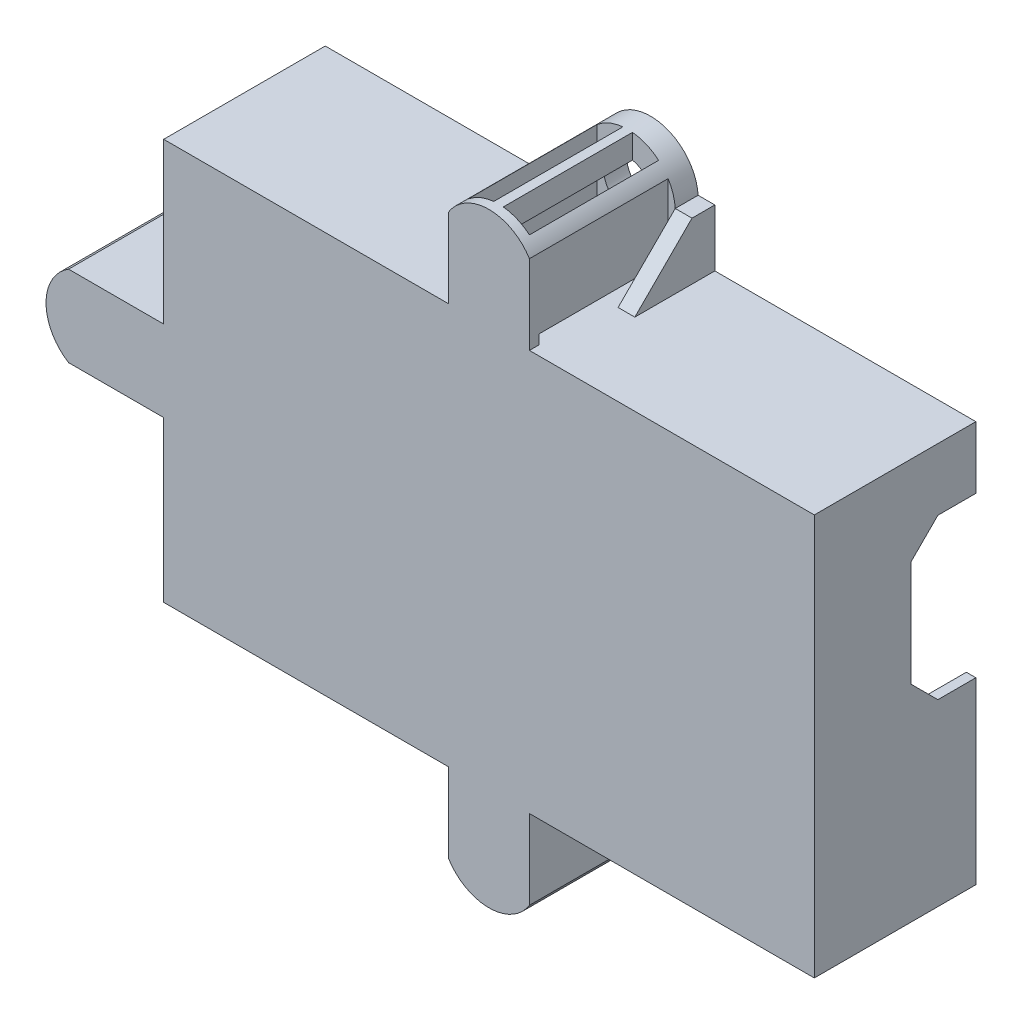
SolidWorks part; units mm, degrees
ref_plane "Front Plane" through (0, 0, 0) normal (0, 0, 1) x (1, 0, 0)
ref_plane "Top Plane" through (0, 0, 0) normal (0, 1, 0) x (1, 0, 0)
ref_plane "Right Plane" through (0, 0, 0) normal (1, 0, 0) x (0, 0, -1)
sketch "Sketch1" plane through (0, 0, 0) normal (0, 0, 1) x (1, 0, 0)
  line L0 (-16.375, 9.825) -> (16.375, -9.825) construction
  line L1 (-16.375, -9.825) -> (-16.575, -9.825) construction
  line L2 (16.575, 10.025) -> (-16.575, 10.025)
  line L3 (16.575, 10.025) -> (16.575, -10.025)
  line L4 (-16.375, 9.825) -> (-16.375, -9.825)
  line L5 (-16.375, -9.825) -> (16.375, -9.825)
  line L6 (16.375, -9.825) -> (16.375, 9.825)
  line L7 (16.375, 9.825) -> (-16.375, 9.825)
  line L8 (-16.375, 9.825) -> (-16.375, -9.825)
  line L9 (-16.375, -9.825) -> (16.375, -9.825)
  line L10 (16.375, -9.825) -> (16.375, 9.825)
  line L11 (16.375, 9.825) -> (-16.375, 9.825)
  line L12 (16.575, -10.025) -> (-16.575, -10.025)
  line L13 (-16.575, 10.025) -> (-16.575, -10.025)
  line L14 (16.575, 10.025) -> (-16.575, -10.025) construction
  line L15 (-13.9701, -11.875) -> (-3.4641, -11.875)
  line L18 (3.4641, -11.875) -> (13.9701, -11.875)
  line L19 (14.8161, -12.3418) -> (24.6724, -27.981)
  line L20 (31.4404, -23.7156) -> (19.404, -4.6171)
  line L21 (19.25, -4.084) -> (19.25, 4.084)
  line L22 (19.404, 4.6171) -> (31.4404, 23.7156)
  line L23 (24.6724, 27.981) -> (14.8161, 12.3418)
  line L24 (13.9701, 11.875) -> (3.4641, 11.875)
  line L25 (-3.4641, 11.875) -> (-13.9701, 11.875)
  line L26 (-14.8161, 12.3418) -> (-24.6724, 27.981)
  line L27 (-31.4404, 23.7156) -> (-19.404, 4.6171)
  line L28 (-19.25, 4.084) -> (-19.25, 3.4641)
  line L29 (-19.25, -3.4641) -> (-19.25, -4.084)
  line L30 (-19.404, -4.6171) -> (-31.4404, -23.7156)
  line L31 (-24.6724, -27.981) -> (-14.8161, -12.3418)
  line L32 (-13.9701, -11.875) -> (-3.4641, -11.875)
  line L33 (3.4641, -11.875) -> (13.9701, -11.875)
  line L34 (14.8161, -12.3418) -> (24.6724, -27.981)
  line L35 (31.4404, -23.7156) -> (19.404, -4.6171)
  line L36 (19.25, -4.084) -> (19.25, 4.084)
  line L37 (19.404, 4.6171) -> (31.4404, 23.7156)
  line L38 (24.6724, 27.981) -> (14.8161, 12.3418)
  line L39 (13.9701, 11.875) -> (3.4641, 11.875)
  line L40 (-3.4641, 11.875) -> (-13.9701, 11.875)
  line L41 (-14.8161, 12.3418) -> (-24.6724, 27.981)
  line L42 (-31.4404, 23.7156) -> (-19.404, 4.6171)
  line L43 (-19.25, 4.084) -> (-19.25, 3.4641)
  line L44 (-19.25, -3.4641) -> (-19.25, -4.084)
  line L45 (-19.404, -4.6171) -> (-31.4404, -23.7156)
  line L46 (-24.6724, -27.981) -> (-14.8161, -12.3418)
  line L47 (16.575, -10.025) -> (-16.575, 10.025) construction
  line L48 (-16.375, -9.825) -> (-16.375, -10.025) construction
  line L49 (-16.575, -10.025) -> (-17.075, -10.025) construction
  line L50 (17.075, 10.525) -> (-17.075, 10.525)
  line L51 (17.075, 10.525) -> (17.075, -10.525)
  line L52 (17.075, -10.525) -> (-17.075, -10.525)
  line L53 (-17.075, 10.525) -> (-17.075, -10.525)
  line L54 (17.075, 10.525) -> (-17.075, -10.525) construction
  line L55 (17.075, -10.525) -> (-17.075, 10.525) construction
  line L56 (-16.575, -10.025) -> (-16.575, -10.525) construction
  line L57 (-20.3929, -2.4744) -> (-17.075, -2.4744)
  line L58 (-20.3929, 2.4744) -> (-17.075, 2.4744)
  line L59 (-2.4744, -13.0179) -> (-2.4744, -10.525)
  line L60 (2.4744, -13.0179) -> (2.4744, -10.525)
  line L61 (-2.4744, 13.0179) -> (-2.4744, 10.525)
  line L62 (2.4744, 13.0179) -> (2.4744, 10.525)
  circle A0 centre (0, -13.375) radius 1.25
  circle A1 centre (-20.75, 0) radius 1.25
  circle A2 centre (0, 13.375) radius 1.25
  arc A32 (-2.4744, -13.0179) -> (-3.4641, -11.875) centre (-3.4641, -12.875) ccw
  arc A33 (-2.4744, -13.0179) -> (2.4744, -13.0179) centre (0, -13.375) ccw
  arc A34 (3.4641, -11.875) -> (2.4744, -13.0179) centre (3.4641, -12.875) ccw
  arc A35 (14.8161, -12.3418) -> (13.9701, -11.875) centre (13.9701, -12.875) ccw
  arc A36 (24.7505, -28.8963) -> (24.6724, -27.981) centre (23.8264, -28.5142) ccw
  arc A37 (24.7505, -28.8963) -> (32.2325, -24.1809) centre (31.8198, -31.8198) ccw
  arc A38 (31.4404, -23.7156) -> (32.2325, -24.1809) centre (32.2864, -23.1824) ccw
  arc A39 (19.25, -4.084) -> (19.404, -4.6171) centre (20.25, -4.084) ccw
  arc A40 (19.404, 4.6171) -> (19.25, 4.084) centre (20.25, 4.084) ccw
  arc A41 (32.2325, 24.1809) -> (31.4404, 23.7156) centre (32.2864, 23.1824) ccw
  arc A42 (32.2325, 24.1809) -> (24.7505, 28.8963) centre (31.8198, 31.8198) ccw
  arc A43 (24.6724, 27.981) -> (24.7505, 28.8963) centre (23.8264, 28.5142) ccw
  arc A44 (13.9701, 11.875) -> (14.8161, 12.3418) centre (13.9701, 12.875) ccw
  arc A45 (2.4744, 13.0179) -> (3.4641, 11.875) centre (3.4641, 12.875) ccw
  arc A46 (2.4744, 13.0179) -> (-2.4744, 13.0179) centre (0, 13.375) ccw
  arc A47 (-3.4641, 11.875) -> (-2.4744, 13.0179) centre (-3.4641, 12.875) ccw
  arc A48 (-14.8161, 12.3418) -> (-13.9701, 11.875) centre (-13.9701, 12.875) ccw
  arc A49 (-24.7505, 28.8963) -> (-24.6724, 27.981) centre (-23.8264, 28.5142) ccw
  arc A50 (-24.7505, 28.8963) -> (-32.2325, 24.1809) centre (-31.8198, 31.8198) ccw
  arc A51 (-31.4404, 23.7156) -> (-32.2325, 24.1809) centre (-32.2864, 23.1824) ccw
  arc A52 (-19.25, 4.084) -> (-19.404, 4.6171) centre (-20.25, 4.084) ccw
  arc A53 (-20.3929, 2.4744) -> (-19.25, 3.4641) centre (-20.25, 3.4641) ccw
  arc A54 (-20.3929, 2.4744) -> (-20.3929, -2.4744) centre (-20.75, 0) ccw
  arc A55 (-19.25, -3.4641) -> (-20.3929, -2.4744) centre (-20.25, -3.4641) ccw
  arc A56 (-19.404, -4.6171) -> (-19.25, -4.084) centre (-20.25, -4.084) ccw
  arc A57 (-32.2325, -24.1809) -> (-31.4404, -23.7156) centre (-32.2864, -23.1824) ccw
  arc A58 (-32.2325, -24.1809) -> (-24.7505, -28.8963) centre (-31.8198, -31.8198) ccw
  arc A59 (-24.6724, -27.981) -> (-24.7505, -28.8963) centre (-23.8264, -28.5142) ccw
  arc A60 (-13.9701, -11.875) -> (-14.8161, -12.3418) centre (-13.9701, -12.875) ccw
  arc A61 (-2.4744, -13.0179) -> (-3.4641, -11.875) centre (-3.4641, -12.875) ccw
  arc A62 (-2.4744, -13.0179) -> (2.4744, -13.0179) centre (0, -13.375) ccw
  arc A63 (3.4641, -11.875) -> (2.4744, -13.0179) centre (3.4641, -12.875) ccw
  arc A64 (14.8161, -12.3418) -> (13.9701, -11.875) centre (13.9701, -12.875) ccw
  arc A65 (24.7505, -28.8963) -> (24.6724, -27.981) centre (23.8264, -28.5142) ccw
  arc A66 (24.7505, -28.8963) -> (32.2325, -24.1809) centre (31.8198, -31.8198) ccw
  arc A67 (31.4404, -23.7156) -> (32.2325, -24.1809) centre (32.2864, -23.1824) ccw
  arc A68 (19.25, -4.084) -> (19.404, -4.6171) centre (20.25, -4.084) ccw
  arc A69 (19.404, 4.6171) -> (19.25, 4.084) centre (20.25, 4.084) ccw
  arc A70 (32.2325, 24.1809) -> (31.4404, 23.7156) centre (32.2864, 23.1824) ccw
  arc A71 (32.2325, 24.1809) -> (24.7505, 28.8963) centre (31.8198, 31.8198) ccw
  arc A72 (24.6724, 27.981) -> (24.7505, 28.8963) centre (23.8264, 28.5142) ccw
  arc A73 (13.9701, 11.875) -> (14.8161, 12.3418) centre (13.9701, 12.875) ccw
  arc A74 (2.4744, 13.0179) -> (3.4641, 11.875) centre (3.4641, 12.875) ccw
  arc A75 (2.4744, 13.0179) -> (-2.4744, 13.0179) centre (0, 13.375) ccw
  arc A76 (-3.4641, 11.875) -> (-2.4744, 13.0179) centre (-3.4641, 12.875) ccw
  arc A77 (-14.8161, 12.3418) -> (-13.9701, 11.875) centre (-13.9701, 12.875) ccw
  arc A78 (-24.7505, 28.8963) -> (-24.6724, 27.981) centre (-23.8264, 28.5142) ccw
  arc A79 (-24.7505, 28.8963) -> (-32.2325, 24.1809) centre (-31.8198, 31.8198) ccw
  arc A80 (-31.4404, 23.7156) -> (-32.2325, 24.1809) centre (-32.2864, 23.1824) ccw
  arc A81 (-19.25, 4.084) -> (-19.404, 4.6171) centre (-20.25, 4.084) ccw
  arc A82 (-20.3929, 2.4744) -> (-19.25, 3.4641) centre (-20.25, 3.4641) ccw
  arc A83 (-20.3929, 2.4744) -> (-20.3929, -2.4744) centre (-20.75, 0) ccw
  arc A84 (-19.25, -3.4641) -> (-20.3929, -2.4744) centre (-20.25, -3.4641) ccw
  arc A85 (-19.404, -4.6171) -> (-19.25, -4.084) centre (-20.25, -4.084) ccw
  arc A86 (-32.2325, -24.1809) -> (-31.4404, -23.7156) centre (-32.2864, -23.1824) ccw
  arc A87 (-32.2325, -24.1809) -> (-24.7505, -28.8963) centre (-31.8198, -31.8198) ccw
  arc A88 (-24.6724, -27.981) -> (-24.7505, -28.8963) centre (-23.8264, -28.5142) ccw
  arc A89 (-13.9701, -11.875) -> (-14.8161, -12.3418) centre (-13.9701, -12.875) ccw
  point P6 (0, 0)
  point P25 (0, 0)
  dimension "D4" = 0.5
  dimension "D5" = 2.5
  dimension "D1" = 0
  dimension "D2" = 0
  dimension "D3" = 0.2
extrude "Boss-Extrude1" add sketch "Sketch1" along normal offset from surface (7.98 mm away) 2.5 contours A84 L57 L53 L58 A82 A83 | L50 L53 L52 L51 L13 L2 L3 L12 | A63 L60 L52 L59 A61 A62 | A76 L61 L50 L62 A74 A75 region at (-2.4011, -11.6286, 0) region at (-9.7747, -10.1238, 0) region at (-18.5911, -2.3949, 0) region at (0, 10.5982, 0) offset beyond the face yes
sketch "Sketch2" plane through (0, 0, 7.98) normal (0, 0, 1) x (1, 0, 0)
  line L0 (-2.5, 10.525) -> (2.4744, 10.525)
  line L1 (-17.075, 2.5) -> (-17.075, -2.5)
  line L2 (-2.5, -10.525) -> (2.4744, -10.525)
  line L6 (-20.1071, -2.4744) -> (-17.075, -2.4744)
  line L7 (-20.1071, -2.4744) -> (-17.075, -2.4744)
  line L8 (-17.075, -2.4744) -> (-17.075, -10.525)
  line L9 (-17.075, -2.4744) -> (-17.075, -10.525)
  line L20 (-17.075, -10.525) -> (-2.4744, -10.525)
  line L21 (-17.075, -10.525) -> (-2.4744, -10.525)
  line L22 (-2.4744, -10.525) -> (-2.4744, -12.7321)
  line L23 (-2.4744, -10.525) -> (-2.4744, -12.7321)
  line L24 (2.4744, -12.7321) -> (2.4744, -10.525)
  line L25 (2.4744, -12.7321) -> (2.4744, -10.525)
  line L26 (2.4744, -10.525) -> (17.075, -10.525)
  line L27 (2.4744, -10.525) -> (17.075, -10.525)
  line L28 (17.075, -10.525) -> (17.075, 10.525)
  line L29 (17.075, -10.525) -> (17.075, 10.525)
  line L30 (17.075, 10.525) -> (2.4744, 10.525)
  line L31 (17.075, 10.525) -> (2.4744, 10.525)
  line L32 (2.4744, 10.525) -> (2.4744, 12.7321)
  line L33 (2.4744, 10.525) -> (2.4744, 12.7321)
  line L34 (-2.4744, 12.7321) -> (-2.4744, 10.525)
  line L35 (-2.4744, 12.7321) -> (-2.4744, 10.525)
  line L36 (-2.4744, 10.525) -> (-17.075, 10.525)
  line L37 (-2.4744, 10.525) -> (-17.075, 10.525)
  line L38 (-17.075, 10.525) -> (-17.075, 2.4744)
  line L39 (-17.075, 10.525) -> (-17.075, 2.4744)
  line L40 (-17.075, 2.4744) -> (-20.1071, 2.4744)
  line L41 (-17.075, 2.4744) -> (-20.1071, 2.4744)
  arc A9 (-20.1071, -2.4744) -> (-20.3929, -2.4744) centre (-20.25, -3.4641) ccw
  arc A10 (-20.1071, -2.4744) -> (-20.3929, -2.4744) centre (-20.25, -3.4641) ccw
  arc A11 (-2.4744, -13.0179) -> (-2.4744, -12.7321) centre (-3.4641, -12.875) ccw
  arc A12 (-2.4744, -13.0179) -> (-2.4744, -12.7321) centre (-3.4641, -12.875) ccw
  arc A13 (-2.4744, -13.0179) -> (2.4744, -13.0179) centre (0, -13.375) ccw
  arc A14 (-2.4744, -13.0179) -> (2.4744, -13.0179) centre (0, -13.375) ccw
  arc A15 (2.4744, -12.7321) -> (2.4744, -13.0179) centre (3.4641, -12.875) ccw
  arc A16 (2.4744, -12.7321) -> (2.4744, -13.0179) centre (3.4641, -12.875) ccw
  arc A17 (2.4744, 13.0179) -> (2.4744, 12.7321) centre (3.4641, 12.875) ccw
  arc A18 (2.4744, 13.0179) -> (2.4744, 12.7321) centre (3.4641, 12.875) ccw
  arc A19 (2.4744, 13.0179) -> (-2.4744, 13.0179) centre (0, 13.375) ccw
  arc A20 (2.4744, 13.0179) -> (-2.4744, 13.0179) centre (0, 13.375) ccw
  arc A21 (-2.4744, 12.7321) -> (-2.4744, 13.0179) centre (-3.4641, 12.875) ccw
  arc A22 (-2.4744, 12.7321) -> (-2.4744, 13.0179) centre (-3.4641, 12.875) ccw
  arc A23 (-20.3929, 2.4744) -> (-20.1071, 2.4744) centre (-20.25, 3.4641) ccw
  arc A24 (-20.3929, 2.4744) -> (-20.1071, 2.4744) centre (-20.25, 3.4641) ccw
  arc A25 (-20.3929, 2.4744) -> (-20.3929, -2.4744) centre (-20.75, 0) ccw
  arc A26 (-20.3929, 2.4744) -> (-20.3929, -2.4744) centre (-20.75, 0) ccw
  dimension "D1" = 0
extrude "Cut-Extrude1" cut sketch "Sketch2" against normal offset from surface (6.78 mm away) 1.2 contours L0 | L1 | L2 region at (0, 12.9704, 7.98) region at (-19.9289, 0, 7.98) region at (0, -12.9704, 7.98) up to face at (-5.364, 0, 0)
sketch "Sketch3" plane through (17.075, 0, 0) normal (1, 0, 0) x (0, 0, -1)
  line L0 (0, 10.525) -> (0, -10.525) construction
  line L1 (0, 7.265) -> (-3.395, 7.265)
  line L2 (0, 7.265) -> (0, -1.115)
  line L3 (0, -1.115) -> (-3.395, -1.115)
  line L4 (-3.395, 7.265) -> (-3.395, -1.115)
  line L6 (-1.3, 7.065) -> (-1.3, 7.265) construction
  line L7 (-1.3, -0.915) -> (-1.3, -1.115) construction
  line L8 (-3.195, 5.375) -> (-3.395, 5.375) construction
  dimension "D1" = 0.2
extrude "Cut-Extrude2" cut sketch "Sketch3" against normal up to next
chamfer "Chamfer1" distance 1.4 angle 45 2 edges at (16.825, -1.115, 3.395) (16.825, 7.265, 3.395)
sketch "Sketch4" plane through (0, 0, 7.98) normal (0, 0, 1) x (1, 0, 0)
  line L4 (-17.075, 10.525) -> (-17.075, -10.525)
  line L8 (-17.075, 10.525) -> (-17.075, -10.525)
  line L17 (-17.075, -10.525) -> (17.075, -10.525)
  line L18 (-17.075, -10.525) -> (17.075, -10.525)
  line L25 (17.075, -10.525) -> (17.075, 10.525)
  line L26 (17.075, -10.525) -> (17.075, 10.525)
  line L27 (17.075, 10.525) -> (-17.075, 10.525)
  line L28 (17.075, 10.525) -> (-17.075, 10.525)
  dimension "D1" = 0
extrude "Boss-Extrude2" add sketch "Sketch4" along normal blind 0.5
sketch "Sketch8" plane through (-17.075, 0, 0) normal (-1, 0, 0) x (0, 0, 1)
  line L1 (5.93, 3.385) -> (7.98, 3.385)
  line L2 (5.93, 3.385) -> (5.93, -3.385)
  line L3 (5.93, -3.385) -> (7.98, -3.385)
  line L4 (7.98, 3.385) -> (7.98, -3.385)
  line L7 (7.08, 3.385) -> (5.93, 3.385) construction
  line L8 (5.93, -3.385) -> (7.08, -3.385) construction
  line L9 (5.93, 3.385) -> (5.93, 2.4) construction
  line L10 (7.98, -3.985) -> (7.98, -2.4) construction
extrude "Cut-Extrude3" cut sketch "Sketch8" against normal up to next
sketch "Sketch9" plane through (0, 0, 7.98) normal (0, 0, -1) x (-1, 0, 0)
  line L1 (16.575, 2.4) -> (17.075, 2.4)
  line L2 (16.575, 2.4) -> (16.575, 3.385)
  line L3 (16.575, 3.385) -> (17.075, 3.385)
  line L4 (17.075, 2.4) -> (17.075, 3.385)
  line L5 (16.575, -2.4) -> (17.075, -2.4)
  line L6 (16.575, -2.4) -> (16.575, -3.385)
  line L7 (16.575, -3.385) -> (17.075, -3.385)
  line L8 (17.075, -2.4) -> (17.075, -3.385)
extrude "Boss-Extrude6" add sketch "Sketch9" along normal blind 0.8
sketch "Sketch11" plane through (0, 0, 7.98) normal (0, 0, -1) x (-1, 0, 0)
  line L24 (16.675, -4.085) -> (16.675, -2.3)
  line L25 (16.675, -2.3) -> (15.385, -2.3)
  line L26 (15.385, -2.3) -> (15.385, 2.3)
  line L27 (15.385, 2.3) -> (16.675, 2.3)
  line L28 (16.675, 2.3) -> (16.675, 4.085)
  line L29 (16.675, 4.085) -> (10.255, 4.085)
  line L30 (10.255, 4.085) -> (10.255, 2.4)
  line L31 (10.255, 2.4) -> (5.655, 2.4)
  line L32 (5.655, 2.4) -> (5.655, -2.4)
  line L33 (5.655, -2.4) -> (10.255, -2.4)
  line L34 (10.255, -2.4) -> (10.255, -4.085)
  line L35 (10.255, -4.085) -> (16.675, -4.085)
  line L36 (16.675, -4.085) -> (16.675, -2.3)
  line L37 (16.675, -2.3) -> (15.385, -2.3)
  line L38 (15.385, -2.3) -> (15.385, 2.3)
  line L39 (15.385, 2.3) -> (16.675, 2.3)
  line L40 (16.675, 2.3) -> (16.675, 4.085)
  line L41 (16.675, 4.085) -> (10.255, 4.085)
  line L42 (10.255, 4.085) -> (10.255, 2.4)
  line L43 (10.255, 2.4) -> (5.655, 2.4)
  line L44 (5.655, 2.4) -> (5.655, -2.4)
  line L45 (5.655, -2.4) -> (10.255, -2.4)
  line L46 (10.255, -2.4) -> (10.255, -4.085)
  line L47 (10.255, -4.085) -> (16.675, -4.085)
  line L48 (5.655, 1.9) -> (3.655, 1.9)
  line L49 (3.655, 0) -> (17.385, 0) construction
  line L50 (5.655, -1.9) -> (3.655, -1.9)
  line L51 (16.575, 6.085) -> (16.575, 4.085)
  line L53 (16.575, 10.025) -> (16.575, 2.4) construction
  line L54 (16.575, -6.085) -> (16.575, -4.085)
  line L55 (16.575, -2.4) -> (16.575, -10.025) construction
  line L60 (18.675, -6.085) -> (18.675, -0.3)
  line L61 (18.675, -0.3) -> (17.385, -0.3)
  line L62 (17.385, -0.3) -> (17.385, 0.3)
  line L63 (17.385, 0.3) -> (18.675, 0.3)
  line L64 (18.675, 0.3) -> (18.675, 6.085)
  line L65 (18.675, 6.085) -> (8.255, 6.085)
  line L66 (8.255, 6.085) -> (8.255, 4.4)
  line L67 (8.255, 4.4) -> (3.655, 4.4)
  line L68 (3.655, 4.4) -> (3.655, -4.4)
  line L69 (3.655, -4.4) -> (8.255, -4.4)
  line L70 (8.255, -4.4) -> (8.255, -6.085)
  line L71 (8.255, -6.085) -> (18.675, -6.085)
  line L72 (18.675, -6.085) -> (18.675, -0.3)
  line L73 (18.675, -0.3) -> (17.385, -0.3)
  line L74 (17.385, -0.3) -> (17.385, 0.3)
  line L75 (17.385, 0.3) -> (18.675, 0.3)
  line L76 (18.675, 0.3) -> (18.675, 6.085)
  line L77 (18.675, 6.085) -> (8.255, 6.085)
  line L78 (8.255, 6.085) -> (8.255, 4.4)
  line L79 (8.255, 4.4) -> (3.655, 4.4)
  line L80 (3.655, 4.4) -> (3.655, -4.4)
  line L81 (3.655, -4.4) -> (8.255, -4.4)
  line L82 (8.255, -4.4) -> (8.255, -6.085)
  line L83 (8.255, -6.085) -> (18.675, -6.085)
  line M27 (16.575, -10.025) -> (16.575, -2.4)
  line M31 (16.575, 2.4) -> (16.575, 10.025)
  dimension "D3" = 0.5
  dimension "D1" = 0.1
  dimension "D2" = 2.1
extrude "Boss-Extrude7" add sketch "Sketch11" along normal blind 2.5 contours L79 L80 L48 L44 L43 L42 L41 L77 L78 M31 | L82 L83 L47 L46 L45 L44 L50 L80 L81 M27 region at (-9.8383, -4.2692, 7.98) region at (-9.8383, 4.2692, 7.98)
sketch "Sketch12" plane through (0, 0, 7.98) normal (0, 0, -1) x (-1, 0, 0)
  line L0 (16.575, -6.085) -> (16.575, -10.025) construction
  line L1 (-3.0335, 0) -> (1.6631, 0) construction
  line L2 (16.575, 8.055) -> (14.605, 8.055)
  line L3 (16.575, 8.055) -> (16.575, 6.085)
  line L4 (16.575, 6.085) -> (14.605, 6.085)
  line L5 (16.575, -8.055) -> (14.605, -8.055)
  line L6 (16.575, -8.055) -> (16.575, -6.085)
  line L7 (16.575, -6.085) -> (14.605, -6.085)
  line L8 (14.605, -8.055) -> (14.605, -6.085)
  line L9 (8.255, -6.085) -> (16.575, -6.085) construction
  line L10 (14.605, 8.055) -> (14.605, 6.085)
  line L11 (-16.575, 10.025) -> (-16.575, -10.025) construction
  line L12 (-14.605, 2) -> (-16.575, 2)
  line L13 (-14.605, 2) -> (-14.605, -2)
  line L14 (-14.605, -2) -> (-16.575, -2)
  line L15 (-16.575, 2) -> (-16.575, -2)
  line L16 (-14.605, 2) -> (-16.575, -2) construction
  line L17 (-14.605, -2) -> (-16.575, 2) construction
  point P16 (-15.59, 0)
  dimension "D1" = 4
extrude "Boss-Extrude8" add sketch "Sketch12" along normal up to surface (3.95 mm away)
sketch "Sketch13" plane through (-17.075, 0, 0) normal (-1, 0, 0) x (0, 0, 1)
  line L0 (7.18, 2.4) -> (7.18, 3.385) construction
  line L1 (7.98, 2.4) -> (7.18, 2.4)
  line L2 (7.98, 2.4) -> (7.98, 2.9)
  line L3 (7.98, 2.9) -> (7.18, 2.9)
  line L4 (7.18, 2.4) -> (7.18, 2.9)
  line L5 (5.93, 0) -> (7.98, 0) construction
  line L6 (7.18, 3.385) -> (5.43, 3.385)
  line L7 (7.18, 3.385) -> (7.18, 3.885)
  line L8 (7.18, 3.885) -> (5.43, 3.885)
  line L9 (5.43, 3.385) -> (5.43, 3.885)
  line L10 (5.93, 3.385) -> (5.93, -3.385) construction
  line L11 (7.98, -2) -> (7.98, 2) construction
  line L12 (5.43, 1.6925) -> (5.93, 1.6925) construction
  line L13 (5.43, 3.385) -> (5.93, 3.385)
  line L14 (5.43, 3.385) -> (5.43, -3.385)
  line L15 (5.93, 0) -> (5.93, -3.385)
  line L16 (5.93, 3.385) -> (5.93, 0)
  line L17 (7.98, -2.4) -> (7.98, -2.9)
  line L18 (7.98, -2.9) -> (7.18, -2.9)
  line L19 (7.18, -3.385) -> (7.18, -3.885)
  line L20 (7.18, -3.885) -> (5.43, -3.885)
  line L21 (5.43, -3.385) -> (5.43, -3.885)
  line L22 (5.43, 3.385) -> (5.43, -3.385)
  line L23 (1.2, -2.5) -> (1.2, 2.5) construction
  line L24 (0, 3.3744) -> (1.2, 3.3744)
  line L25 (0, 3.3744) -> (0, 5.8744)
  line L26 (0, 5.8744) -> (1.2, 5.8744)
  line L27 (1.2, 3.3744) -> (1.2, 5.8744)
  line L28 (1.2, 2.4744) -> (0, 2.4744) construction
  line L29 (0, 10.525) -> (0, 2.4744) construction
  line M12 (7.98, -2.4) -> (7.18, -2.4)
  line M13 (7.18, -2.4) -> (7.18, -3.385)
  line M14 (7.18, -3.385) -> (5.93, -3.385)
  line M15 (5.93, -3.385) -> (5.93, 3.385)
  line M16 (5.93, 3.385) -> (7.18, 3.385)
  line M17 (7.18, 3.385) -> (7.18, 2.4)
  line M18 (7.18, 2.4) -> (7.98, 2.4)
  line M22 (0, 10.525) -> (0, 2.4744)
  dimension "D1" = 0.5
  dimension "D2" = 2.5
  dimension "D3" = 0.9
extrude "Cut-Extrude4" cut sketch "Sketch13" against normal up to next contours L9 L6 L7 L8 M16 | L2 L3 M17 M18 | L14 L21 L20 L19 L6 M14 M15 | L18 L17 M12 M13 | L24 L27 L26 M22 region at (-17.075, -2.65, 7.58) region at (-17.075, 3.635, 6.305) region at (-17.075, 2.65, 7.58) region at (-17.075, -0.7466, 5.8084) region at (-17.075, 4.6244, 0.6)
sketch "Sketch14" plane through (0, 0, 5.48) normal (0, 0, -1) x (-1, 0, 0)
  line L0 (16.575, 4.085) -> (10.255, 4.085) construction
  line L1 (16.575, 6.085) -> (14.175, 6.085)
  line L2 (16.575, 6.085) -> (16.575, 3.685)
  line L3 (16.575, 3.685) -> (14.175, 3.685)
  line L4 (14.175, 6.085) -> (14.175, 3.685)
  line L5 (3.655, 1.9) -> (3.655, -1.9) construction
  line L6 (3.655, 0) -> (16.575, 0) construction
  line L8 (16.575, -6.085) -> (16.575, -3.685)
  line L9 (16.575, -6.085) -> (14.175, -6.085)
  line L10 (14.175, -6.085) -> (14.175, -3.685)
  line L11 (16.575, -3.685) -> (14.175, -3.685)
  line L12 (5.655, 2.4) -> (5.655, 1.9) construction
  line L13 (3.655, 4.4) -> (5.655, 4.4)
  line L14 (3.655, 4.4) -> (3.655, 1.5)
  line L15 (3.655, 1.5) -> (5.655, 1.5)
  line L16 (5.655, 4.4) -> (5.655, 1.5)
  line L17 (15.375, 3.685) -> (15.375, 4.085) construction
  line L18 (16.575, 4.085) -> (10.255, 4.085) construction
  line L19 (4.655, 1.5) -> (4.655, 1.9) construction
  line L20 (5.655, 1.9) -> (3.655, 1.9) construction
  line L21 (3.655, -4.4) -> (5.655, -4.4)
  line L22 (5.655, -4.4) -> (5.655, -1.5)
  line L23 (3.655, -1.5) -> (5.655, -1.5)
  line L24 (3.655, -4.4) -> (3.655, -1.5)
  line L25 (16.575, 3.3744) -> (16.575, -10.025) construction
  dimension "D1" = 0.4
extrude "Boss-Extrude9" add sketch "Sketch14" along normal blind 0.6
ref_plane "Plane1" through (0, 0, 2.95) normal (0, 0, -1) x (-1, 0, 0)
sketch "Sketch16" plane through (0, 0, 2.95) normal (0, 0, -1) x (-1, 0, 0)
  line L0 (-16.575, 10.025) -> (16.575, 10.025) construction
  line L1 (6.075, 10.025) -> (8.575, 10.025)
  line L2 (6.075, 10.025) -> (6.075, 9.325)
  line L3 (6.075, 9.325) -> (8.575, 9.325)
  line L4 (8.575, 10.025) -> (8.575, 9.325)
  line L6 (16.575, 10.025) -> (16.575, 5.8744) construction
  line L8 (-16.575, 10.025) -> (-14.075, 10.025)
  line L9 (-16.575, 10.025) -> (-16.575, 9.325)
  line L10 (-16.575, 9.325) -> (-14.075, 9.325)
  line L11 (-14.075, 10.025) -> (-14.075, 9.325)
  line L12 (16.575, -10.025) -> (14.075, -10.025)
  line L13 (16.575, -10.025) -> (16.575, -9.325)
  line L14 (16.575, -9.325) -> (14.075, -9.325)
  line L15 (14.075, -10.025) -> (14.075, -9.325)
  line L16 (-16.575, -10.025) -> (-14.075, -10.025)
  line L17 (-16.575, -10.025) -> (-16.575, -9.325)
  line L18 (-16.575, -9.325) -> (-14.075, -9.325)
  line L19 (-14.075, -10.025) -> (-14.075, -9.325)
  dimension "D1" = 2.5
  dimension "D2" = 0.7
  dimension "D3" = 8
extrude "Boss-Extrude13" add sketch "Sketch16" along normal blind 0.8
chamfer "Chamfer2" distance 1 angle 45 2 edges at (-10.255, 3.2425, 5.48) (-10.255, -3.2425, 5.48)
sketch "Sketch17" plane through (0, 0, 1.2) normal (0, 0, 1) x (1, 0, 0)
  line L0 (-23.25, 0) -> (-17.075, 0) construction
  line L1 (-17.075, 10.525) -> (-17.075, -10.525) construction
  line L2 (0, 15.875) -> (0, -15.875) construction
  line L3 (-20.1071, 2.4744) -> (-17.075, 2.4744) construction
  line L4 (-20.075, -3.3744) -> (-17.075, -3.3744)
  line L5 (-20.075, -3.3744) -> (-20.075, 3.3744)
  line L6 (-20.075, 3.3744) -> (-17.075, 3.3744)
  line L7 (-17.075, -3.3744) -> (-17.075, 3.3744)
  line L8 (-20.075, -3.3744) -> (-17.075, 3.3744) construction
  line L9 (-20.075, 3.3744) -> (-17.075, -3.3744) construction
  line L10 (17.075, 10.525) -> (-17.075, 10.525) construction
  line L11 (-3.3744, 10.525) -> (3.3744, 10.525)
  line L12 (-3.3744, 10.525) -> (-3.3744, 13.525)
  line L13 (-20.1071, -2.4744) -> (-17.075, -2.4744)
  line L14 (-17.075, -2.4744) -> (-17.075, 2.4744)
  line L15 (-17.075, 2.4744) -> (-20.1071, 2.4744)
  line L16 (-20.1071, -2.4744) -> (-17.075, -2.4744)
  line L17 (-17.075, -2.4744) -> (-17.075, 2.4744)
  line L18 (-17.075, 2.4744) -> (-20.1071, 2.4744)
  line L19 (-2.4744, 12.7321) -> (-2.4744, 10.525)
  line L20 (-2.4744, 10.525) -> (2.4744, 10.525)
  line L21 (2.4744, 10.525) -> (2.4744, 12.7321)
  line L22 (-2.4744, 12.7321) -> (-2.4744, 10.525)
  line L23 (-2.4744, 10.525) -> (2.4744, 10.525)
  line L24 (2.4744, 10.525) -> (2.4744, 12.7321)
  line L25 (2.4744, -12.7321) -> (2.4744, -10.525)
  line L26 (2.4744, -10.525) -> (-2.4744, -10.525)
  line L27 (-2.4744, -10.525) -> (-2.4744, -12.7321)
  line L28 (2.4744, -12.7321) -> (2.4744, -10.525)
  line L29 (2.4744, -10.525) -> (-2.4744, -10.525)
  line L30 (-2.4744, -10.525) -> (-2.4744, -12.7321)
  line L31 (-3.3744, 13.525) -> (3.3744, 13.525)
  line L32 (3.3744, 10.525) -> (3.3744, 13.525)
  line L33 (-3.3744, 10.525) -> (3.3744, 13.525) construction
  line L34 (-3.3744, 13.525) -> (3.3744, 10.525) construction
  line L35 (-17.075, -10.525) -> (17.075, -10.525) construction
  line L36 (3.3744, -13.525) -> (-3.3744, -13.525)
  line L37 (3.3744, -13.525) -> (3.3744, -10.525)
  line L38 (3.3744, -10.525) -> (-3.3744, -10.525)
  line L39 (-3.3744, -13.525) -> (-3.3744, -10.525)
  line L40 (3.3744, -13.525) -> (-3.3744, -10.525) construction
  line L41 (3.3744, -10.525) -> (-3.3744, -13.525) construction
  arc A0 (-20.3929, 2.4744) -> (-20.3929, -2.4744) centre (-20.75, 0) ccw construction
  arc A1 (2.4744, 13.0179) -> (-2.4744, 13.0179) centre (0, 13.375) ccw construction
  arc A2 (-2.4744, -13.0179) -> (2.4744, -13.0179) centre (0, -13.375) ccw construction
  arc A6 (-20.3929, 2.4744) -> (-20.1071, 2.4744) centre (-20.25, 3.4641) ccw
  arc A7 (-20.3929, 2.4744) -> (-20.3929, -2.4744) centre (-20.75, 0) ccw
  arc A8 (-20.1071, -2.4744) -> (-20.3929, -2.4744) centre (-20.25, -3.4641) ccw
  arc A9 (-20.3929, 2.4744) -> (-20.1071, 2.4744) centre (-20.25, 3.4641) ccw
  arc A10 (-20.3929, 2.4744) -> (-20.3929, -2.4744) centre (-20.75, 0) ccw
  arc A11 (-20.1071, -2.4744) -> (-20.3929, -2.4744) centre (-20.25, -3.4641) ccw
  arc A12 (2.4744, 13.0179) -> (2.4744, 12.7321) centre (3.4641, 12.875) ccw
  arc A13 (2.4744, 13.0179) -> (-2.4744, 13.0179) centre (0, 13.375) ccw
  arc A14 (-2.4744, 12.7321) -> (-2.4744, 13.0179) centre (-3.4641, 12.875) ccw
  arc A15 (2.4744, 13.0179) -> (2.4744, 12.7321) centre (3.4641, 12.875) ccw
  arc A16 (2.4744, 13.0179) -> (-2.4744, 13.0179) centre (0, 13.375) ccw
  arc A17 (-2.4744, 12.7321) -> (-2.4744, 13.0179) centre (-3.4641, 12.875) ccw
  arc A18 (-2.4744, -13.0179) -> (-2.4744, -12.7321) centre (-3.4641, -12.875) ccw
  arc A19 (-2.4744, -13.0179) -> (2.4744, -13.0179) centre (0, -13.375) ccw
  arc A20 (2.4744, -12.7321) -> (2.4744, -13.0179) centre (3.4641, -12.875) ccw
  arc A21 (-2.4744, -13.0179) -> (-2.4744, -12.7321) centre (-3.4641, -12.875) ccw
  arc A22 (-2.4744, -13.0179) -> (2.4744, -13.0179) centre (0, -13.375) ccw
  arc A23 (2.4744, -12.7321) -> (2.4744, -13.0179) centre (3.4641, -12.875) ccw
  point P15 (-18.575, 0)
  point P38 (0, 12.025)
  point P57 (0, -12.025)
  line M26 (2.4744, -12.7321) -> (2.4744, -10.525)
  line M28 (-2.4744, -10.525) -> (-2.4744, -12.7321)
  arc M29 (-2.4744, -12.7321) -> (-2.4744, -13.0179) centre (-3.4641, -12.875) cw
  arc M30 (-2.4744, -13.0179) -> (2.4744, -13.0179) centre (0, -13.375) ccw
  arc M31 (2.4744, -13.0179) -> (2.4744, -12.7321) centre (3.4641, -12.875) cw
  dimension "D1" = 0.9
  dimension "D2" = 3
  dimension "D3" = 0
  dimension "D4" = 0
  dimension "D5" = 0
extrude "Boss-Extrude17" add sketch "Sketch17" against normal up to surface (1.2 mm away) contours L18 L7 L6 L5 | L16 L5 L4 L7 | L22 A17 A16 L31 L12 L11 | A16 A15 L24 L11 L32 L31 | L37 L38 L36 M26 M31 M30 | L39 L36 L38 M30 M29 M28 region at (-18.575, -2.9244, 1.2) region at (-18.575, 2.9244, 1.2) region at (-2.9256, 12.0209, 1.2) region at (2.9256, 12.0209, 1.2) region at (2.9256, -12.0209, 1.2) region at (-2.9256, -12.0209, 1.2) up to face at (-5.9004, -5.5994, 0)
sketch "Sketch18" plane through (0, 0, 1.2) normal (0, 0, 1) x (1, 0, 0)
  line L0 (-17.075, -3.3744) -> (-17.075, 3.3744) construction
  line L1 (-20.075, 3.3744) -> (-17.075, 3.3744)
  line L2 (-20.075, 3.3744) -> (-20.075, 2.4744)
  line L3 (-20.075, 2.4744) -> (-17.075, 2.4744)
  line L4 (-17.075, 3.3744) -> (-17.075, 2.4744)
  line L5 (-17.075, 10.525) -> (-17.075, -10.525) construction
  line L6 (-20.075, -2.4744) -> (-17.075, -2.4744)
  line L7 (-20.075, -2.4744) -> (-20.075, -3.3744)
  line L8 (-20.075, -3.3744) -> (-17.075, -3.3744)
  line L9 (-17.075, -2.4744) -> (-17.075, -3.3744)
  line L10 (17.075, 10.525) -> (-17.075, 10.525) construction
  line L11 (-2.4955, -13.525) -> (-3.3744, -13.525)
  line L12 (-2.4955, -13.525) -> (-2.4955, -10.525)
  line L13 (-2.4955, -10.525) -> (-3.3744, -10.525)
  line L14 (-3.3744, -13.525) -> (-3.3744, -10.525)
  line L15 (2.4955, -13.525) -> (3.3744, -13.525)
  line L16 (2.4955, -13.525) -> (2.4955, -10.525)
  line L17 (2.4955, -10.525) -> (3.3744, -10.525)
  line L18 (3.3744, -13.525) -> (3.3744, -10.525)
  line L19 (-2.4955, 13.525) -> (-3.3744, 13.525)
  line L20 (-2.4955, 13.525) -> (-2.4955, 10.525)
  line L21 (-2.4955, 10.525) -> (-3.3744, 10.525)
  line L22 (-3.3744, 13.525) -> (-3.3744, 10.525)
  line L23 (-3.3744, 10.525) -> (-3.3744, 13.525) construction
  line L25 (2.4955, 13.525) -> (3.3744, 13.525)
  line L26 (2.4955, 13.525) -> (2.4955, 10.525)
  line L27 (2.4955, 10.525) -> (3.3744, 10.525)
  line L28 (3.3744, 13.525) -> (3.3744, 10.525)
extrude "Boss-Extrude18" add sketch "Sketch18" along normal blind 3
chamfer "Chamfer3" distance 3 angle 45 6 edges at (-2.9349, 13.525, 4.2) (2.9349, 13.525, 4.2) (2.9349, -13.525, 4.2) (-2.9349, -13.525, 4.2) (-20.075, -2.9244, 4.2) (-20.075, 2.9244, 4.2)
sketch "Sketch19" plane through (0, 0, 1.2) normal (0, 0, 1) x (1, 0, 0)
  line L0 (2.4955, -13.525) -> (2.4955, -10.525) construction
  line L1 (2.4955, -10.525) -> (-2.4955, -10.525) construction
  line L2 (-2.4955, -10.525) -> (-2.4955, -13.525) construction
  line L3 (-20.1071, -2.4744) -> (-20.075, -2.4744) construction
  line L4 (-20.075, -2.4744) -> (-17.075, -2.4744) construction
  line L5 (-17.075, -2.4744) -> (-17.075, 2.4744) construction
  line L6 (-17.075, 2.4744) -> (-20.075, 2.4744) construction
  line L7 (-20.075, 2.4744) -> (-20.1071, 2.4744) construction
  line L8 (-2.4955, 10.525) -> (2.4955, 10.525) construction
  line L9 (2.4955, 10.525) -> (2.4955, 13.525) construction
  line L10 (-2.4955, 13.525) -> (-2.4955, 10.525) construction
  line L11 (2.4955, -13.525) -> (2.4955, -10.525)
  line L12 (2.4955, -10.525) -> (-2.4955, -10.525)
  line L13 (-2.4955, -10.525) -> (-2.4955, -13.525)
  line L14 (-20.1071, -2.4744) -> (-20.075, -2.4744)
  line L15 (-20.075, -2.4744) -> (-17.075, -2.4744)
  line L16 (-17.075, -2.4744) -> (-17.075, 2.4744)
  line L17 (-17.075, 2.4744) -> (-20.075, 2.4744)
  line L18 (-20.075, 2.4744) -> (-20.1071, 2.4744)
  line L19 (-2.4955, 10.525) -> (2.4955, 10.525)
  line L20 (2.4955, 10.525) -> (2.4955, 13.525)
  line L21 (-2.4955, 13.525) -> (-2.4955, 10.525)
  line L22 (-20.75, 1.25) -> (-20.75, 2.5) construction
  line L23 (-0.25, 16.225) -> (0.25, 16.225)
  line L24 (-0.25, 16.225) -> (-0.25, 10.525)
  line L25 (-0.25, 10.525) -> (0.25, 10.525)
  line L26 (0.25, 16.225) -> (0.25, 10.525)
  line L27 (-0.25, 16.225) -> (0.25, 10.525) construction
  line L28 (-0.25, 10.525) -> (0.25, 16.225) construction
  line L29 (-0.25, -16.225) -> (0.25, -16.225)
  line L30 (-0.25, -16.225) -> (-0.25, -10.525)
  line L31 (-0.25, -10.525) -> (0.25, -10.525)
  line L32 (0.25, -16.225) -> (0.25, -10.525)
  line L33 (-0.25, -16.225) -> (0.25, -10.525) construction
  line L34 (-0.25, -10.525) -> (0.25, -16.225) construction
  line L35 (-24.425, 0.25) -> (-17.075, 0.25)
  line L36 (-24.425, 0.25) -> (-24.425, -0.25)
  line L37 (-24.425, -0.25) -> (-17.075, -0.25)
  line L38 (-17.075, 0.25) -> (-17.075, -0.25)
  line L39 (-24.425, 0.25) -> (-17.075, -0.25) construction
  line L40 (-24.425, -0.25) -> (-17.075, 0.25) construction
  line L41 (-23.25, 0) -> (-17.075, 0) construction
  line L42 (-24.425, 2.125) -> (-17.075, 2.125)
  line L43 (-24.425, 2.125) -> (-24.425, 1.625)
  line L44 (-24.425, 1.625) -> (-17.075, 1.625)
  line L45 (-17.075, 2.125) -> (-17.075, 1.625)
  line L46 (-24.425, 2.125) -> (-17.075, 1.625) construction
  line L47 (-24.425, 1.625) -> (-17.075, 2.125) construction
  line L48 (-24.425, -2.125) -> (-24.425, -1.625)
  line L49 (-24.425, -2.125) -> (-17.075, -2.125)
  line L50 (-24.425, -1.625) -> (-17.075, -1.625)
  line L51 (1.25, 13.375) -> (2.4955, 13.375) construction
  line L52 (0, 16.225) -> (0, 10.525) construction
  line L53 (1.6227, 16.225) -> (2.1227, 16.225)
  line L54 (1.6227, 16.225) -> (1.6227, 10.525)
  line L55 (1.6227, 10.525) -> (2.1227, 10.525)
  line L56 (2.1227, 16.225) -> (2.1227, 10.525)
  line L57 (1.6227, 16.225) -> (2.1227, 10.525) construction
  line L58 (1.6227, 10.525) -> (2.1227, 16.225) construction
  line L59 (-1.6227, 16.225) -> (-1.6227, 10.525)
  line L60 (-2.1227, 16.225) -> (-2.1227, 10.525)
  line L61 (-1.6227, 16.225) -> (-2.1227, 16.225)
  line L62 (1.25, -13.375) -> (2.4955, -13.375) construction
  line L63 (0, -10.525) -> (0, -16.225) construction
  line L64 (2.1227, -16.225) -> (1.6227, -16.225)
  line L65 (2.1227, -16.225) -> (2.1227, -10.525)
  line L66 (2.1227, -10.525) -> (1.6227, -10.525)
  line L67 (1.6227, -16.225) -> (1.6227, -10.525)
  line L68 (2.1227, -16.225) -> (1.6227, -10.525) construction
  line L69 (2.1227, -10.525) -> (1.6227, -16.225) construction
  line L70 (-2.1227, -16.225) -> (-2.1227, -10.525)
  line L71 (-1.6227, -16.225) -> (-1.6227, -10.525)
  line L72 (-2.1227, -16.225) -> (-1.6227, -16.225)
  line L74 (-2.4955, -11.025) -> (2.4955, -11.025)
  line L75 (-2.4955, -11.025) -> (-2.4955, -10.525)
  line L76 (-2.4955, -10.525) -> (2.4955, -10.525)
  line L77 (2.4955, -11.025) -> (2.4955, -10.525)
  line L78 (-2.4955, -11.025) -> (2.4955, -10.525) construction
  line L79 (-2.4955, -10.525) -> (2.4955, -11.025) construction
  line L80 (2.4955, 11.025) -> (-2.4955, 11.025)
  line L81 (2.4955, 11.025) -> (2.4955, 10.525)
  line L82 (2.4955, 10.525) -> (-2.4955, 10.525)
  line L83 (-2.4955, 11.025) -> (-2.4955, 10.525)
  line L84 (2.4955, 11.025) -> (-2.4955, 10.525) construction
  line L85 (2.4955, 10.525) -> (-2.4955, 11.025) construction
  line L86 (-17.575, -2.4744) -> (-17.075, -2.4744)
  line L87 (-17.575, -2.4744) -> (-17.575, 2.4744)
  line L88 (-17.575, 2.4744) -> (-17.075, 2.4744)
  line L89 (-17.075, -2.4744) -> (-17.075, 2.4744)
  line L90 (-17.575, -2.4744) -> (-17.075, 2.4744) construction
  line L91 (-17.575, 2.4744) -> (-17.075, -2.4744) construction
  arc A0 (-2.4955, -13.525) -> (2.4955, -13.525) centre (0, -13.375) ccw construction
  arc A1 (-20.3929, 2.4744) -> (-20.1071, 2.4744) centre (-20.25, 3.4641) ccw construction
  arc A2 (-20.3929, 2.4744) -> (-20.3929, -2.4744) centre (-20.75, 0) ccw construction
  arc A3 (-20.1071, -2.4744) -> (-20.3929, -2.4744) centre (-20.25, -3.4641) ccw construction
  arc A4 (2.4955, 13.525) -> (-2.4955, 13.525) centre (0, 13.375) ccw construction
  arc A5 (-2.4955, -13.525) -> (2.4955, -13.525) centre (0, -13.375) ccw
  arc A6 (-20.3929, 2.4744) -> (-20.1071, 2.4744) centre (-20.25, 3.4641) ccw
  arc A7 (-20.3929, 2.4744) -> (-20.3929, -2.4744) centre (-20.75, 0) ccw
  arc A8 (-20.1071, -2.4744) -> (-20.3929, -2.4744) centre (-20.25, -3.4641) ccw
  arc A9 (2.4955, 13.525) -> (-2.4955, 13.525) centre (0, 13.375) ccw
  circle A10 centre (0, 13.375) radius 1.25 construction
  circle A11 centre (0, 13.375) radius 1.25
  circle A12 centre (-20.75, 0) radius 1.25 construction
  circle A13 centre (-20.75, 0) radius 1.25
  circle A14 centre (0, -13.375) radius 1.25 construction
  circle A15 centre (0, -13.375) radius 1.25
  point P33 (-20.75, 1.875)
  point P47 (-20.75, 1.875)
  point P55 (1.8727, 13.375)
  point P68 (1.8727, -13.375)
  point P79 (0, -10.775)
  point P80 (0, 10.775)
  point P83 (-17.325, 0)
  circle M4 centre (-20.75, 0) radius 1.25
  arc M11 (-20.3929, 2.4744) -> (-20.3929, -2.4744) centre (-20.75, 0) ccw
  dimension "D1" = 0.5
extrude "Boss-Extrude19" add sketch "Sketch19" along normal up to surface (7.28 mm away) contours L44 L87 L42 M11 | L37 L87 L35 M4 | L37 L35 M11 M4 | L49 L87 L50 M11 | L59 A9 L60 L80 | A11 L26 A9 L24 | A11 L24 L80 L26 | L56 A9 L54 L80 | L70 A5 L71 L74 | A15 L32 L74 L30 | A15 L30 A5 L32 | L67 A5 L65 L74 region at (1.8667, -13.0242, 1.2) region at (0, -15.2437, 1.2) region at (0, -11.5792, 1.2) region at (-1.8667, -13.0242, 1.2) region at (-19.9848, -1.87, 1.2) region at (-22.6187, 0, 1.2) region at (-18.5417, 0, 1.2) region at (-19.9848, 1.87, 1.2) region at (-1.8667, 13.0242, 1.2) region at (0, 11.5792, 1.2) region at (0, 15.2437, 1.2) region at (1.8667, 13.0242, 1.2) up to face at (0, 0, 8.48)
sketch "Sketch20" plane through (0, 0, 8.48) normal (0, 0, 1) x (1, 0, 0)
  line L0 (-23.25, 0) -> (-17.075, 0) construction
  line L1 (-17.075, 10.525) -> (-17.075, -10.525) construction
  line L2 (-22.067, -2.125) -> (-17.575, -2.125) construction
  line L3 (-24.425, 2.125) -> (-17.075, 2.125)
  line L4 (-24.425, 2.125) -> (-24.425, -2.125)
  line L5 (-24.425, -2.125) -> (-17.075, -2.125)
  line L6 (-17.075, 2.125) -> (-17.075, -2.125)
  line L7 (-24.425, 2.125) -> (-17.075, -2.125) construction
  line L8 (-24.425, -2.125) -> (-17.075, 2.125) construction
  line L9 (0, 15.875) -> (0, 10.525) construction
  line L10 (2.4955, 10.525) -> (-2.4955, 10.525) construction
  line L11 (-2.1227, 14.6956) -> (-2.1227, 11.025) construction
  line L12 (2.1227, 16.225) -> (-2.1227, 16.225)
  line L13 (2.1227, 16.225) -> (2.1227, 10.525)
  line L14 (2.1227, 10.525) -> (-2.1227, 10.525)
  line L15 (-2.1227, 16.225) -> (-2.1227, 10.525)
  line L16 (2.1227, 16.225) -> (-2.1227, 10.525) construction
  line L17 (2.1227, 10.525) -> (-2.1227, 16.225) construction
  line L18 (0, -15.875) -> (0, -10.525) construction
  line L19 (-17.075, -10.525) -> (17.075, -10.525) construction
  line L20 (2.1227, -14.6956) -> (2.1227, -11.025) construction
  line L21 (-2.1227, -16.225) -> (2.1227, -16.225)
  line L22 (-2.1227, -16.225) -> (-2.1227, -10.525)
  line L23 (-2.1227, -10.525) -> (2.1227, -10.525)
  line L24 (2.1227, -16.225) -> (2.1227, -10.525)
  line L25 (-2.1227, -16.225) -> (2.1227, -10.525) construction
  line L26 (-2.1227, -10.525) -> (2.1227, -16.225) construction
  circle A0 centre (-20.75, 0) radius 2.5
  arc A1 (-22.6498, 1.625) -> (-23.2375, 0.25) centre (-20.75, 0) ccw construction
  arc A2 (0.25, 15.8625) -> (-0.25, 15.8625) centre (0, 13.375) ccw construction
  circle A3 centre (0, 13.375) radius 2.5
  arc A4 (1.6227, 15.2768) -> (0.25, 15.8625) centre (0, 13.375) ccw construction
  arc A5 (-0.25, -15.8625) -> (0.25, -15.8625) centre (0, -13.375) ccw construction
  circle A6 centre (0, -13.375) radius 2.5
  arc A7 (0.25, -15.8625) -> (1.6227, -15.2768) centre (0, -13.375) ccw construction
  point P42 (0, -13.375)
  line M4 (-2.1227, -11.025) -> (-2.1227, -14.6956)
  arc M5 (-2.1227, -14.6956) -> (-1.6227, -15.2768) centre (0, -13.375) ccw
  line M6 (-1.6227, -15.2768) -> (-1.6227, -11.025)
  line M7 (-1.6227, -11.025) -> (-2.1227, -11.025)
extrude "Boss-Extrude20" add sketch "Sketch20" against normal blind 0.5 contours L24 A6 M6 | A6 L22 M6 M5 | A6 L24 L23 L22 M7 M6 | A6 M6 M7 M4 | L3 A0 L5 | A0 L5 L6 L3 | L13 A3 L15 | A3 L15 L14 L13 region at (-20.75, 0, 8.48) region at (-17.8727, 0, 8.48) region at (0, 13.375, 8.48) region at (2.0776, 11.2897, 8.48) region at (-1.8582, -13.375, 8.48) region at (0.1833, -13.375, 8.48) region at (-1.9065, -11.3988, 8.48) region at (0.3902, -10.86, 8.48)
